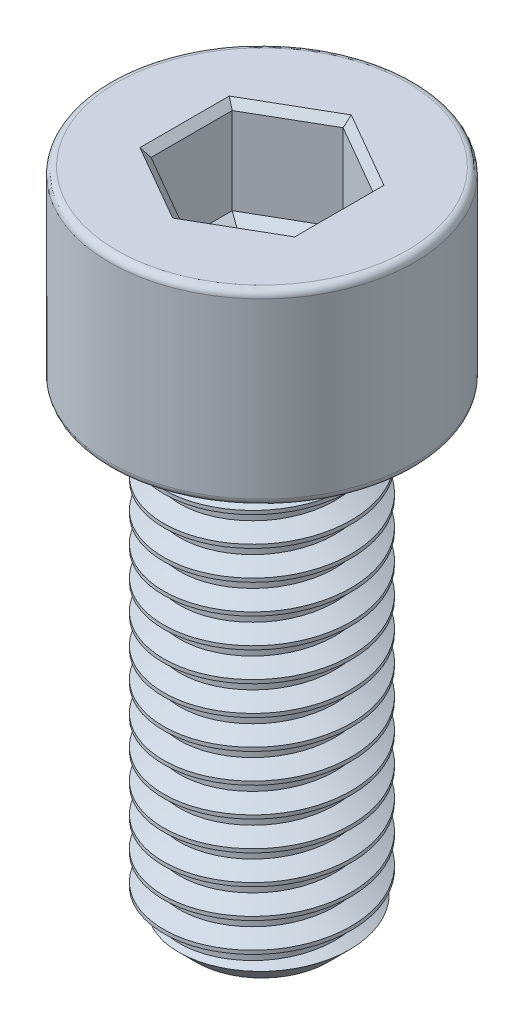
SolidWorks part; units mm, degrees
material "AISI Type A2 Tool Steel"
ref_plane "Front Plane" through (0, 0, 0) normal (0, 0, 1) x (1, 0, 0)
ref_plane "Top Plane" through (0, 0, 0) normal (0, 1, 0) x (1, 0, 0)
ref_plane "Right Plane" through (0, 0, 0) normal (1, 0, 0) x (0, 0, -1)
sketch "Sketch1" plane through (0, 0, 0) normal (0, 1, 0) x (1, 0, 0)
  circle A0 centre (0, 0) radius 4
  dimension "D1" = 8
extrude "Boss-Extrude1" add sketch "Sketch1" along normal blind 20
thread "Thread1" pitch 1.25 method cut profile "Thread Profile1" start angle 0, offset 1.25, length 0, pitch 1.25, diameter 8
ref_plane "Plane1" through (-4, 21.25, 0) normal (0, 0, 1) x (-1, 0, 0)
sketch "Thread Profile1" plane through (-4, 21.25, 0) normal (0, 0, 1) x (-1, 0, 0)
  line L0 (0, 0) -> (0, 1.25) construction
  line L11 (0, 0) -> (0, 1.0937)
  line L12 (0, 1.0937) -> (-0.6766, 0.7031)
  line L13 (-0.6766, 0.7031) -> (-0.6766, 0.3906)
  line L15 (-0.6766, 0.3906) -> (0, 0)
  line L17 (-0.6766, 0.5469) -> (0, 0.5469) construction
  point P2 (0, 0)
  dimension "Pitch" = 1.25
  dimension "Profile_Angle" = 60
  dimension "Profile_Land" = 0.3125
  dimension "Profile_Height" = 0.6766
sketch "Sketch2" plane through (0, 20, 0) normal (0, 1, 0) x (1, 0, 0)
  circle A0 centre (0, 0) radius 6.5
  dimension "D1" = 13
extrude "Boss-Extrude2" add sketch "Sketch2" along normal blind 8
sketch "Sketch5" plane through (0, 0, 0) normal (0, 0, 1) x (1, 0, 0)
  line L0 (0, 0) -> (0, 0.9986) construction
  line L1 (0, 0) -> (4.01, 0) construction
  line L2 (4.01, 0) -> (4.01, 1.2)
  line L3 (4.01, 1.2) -> (2.81, 0)
  line L4 (2.81, 0) -> (4.01, 0)
  dimension "D1" = 1.2
  dimension "D2" = 45
  dimension "D3" = 4.01
revolve "Cut-Revolve1" cut sketch "Sketch5" angle 360 about L0
fillet "Fillet1" radius 0.3 2 edges at (0, 28, 6.5) (0, 20, 6.5)
sketch "Sketch6" plane through (0, 28, 0) normal (0, 1, 0) x (1, 0, 0)
  line L1 (0, 3.4641) -> (-3, 1.7321)
  line L2 (-3, 1.7321) -> (-3, -1.7321)
  line L3 (-3, -1.7321) -> (0, -3.4641)
  line L4 (0, -3.4641) -> (3, -1.7321)
  line L5 (3, -1.7321) -> (3, 1.7321)
  line L6 (3, 1.7321) -> (0, 3.4641)
  circle A0 centre (0, 0) radius 3 construction
  dimension "D1" = 6
extrude "Cut-Extrude1" cut sketch "Sketch6" against normal blind 4
chamfer "Chamfer1" distance 0.3 angle 45 6 edges at (-3, 28, 0) (-1.5, 28, 2.5981) (1.5, 28, 2.5981) (3, 28, 0) (1.5, 28, -2.5981) (-1.5, 28, -2.5981)
sketch "Sketch7" plane through (0, 24, 0) normal (0, 1, 0) x (1, 0, 0)
  line L1 (0, 3.4641) -> (-3, 1.7321)
  line L2 (-3, 1.7321) -> (-3, -1.7321)
  line L3 (-3, -1.7321) -> (0, -3.4641)
  line L4 (0, -3.4641) -> (3, -1.7321)
  line L5 (3, -1.7321) -> (3, 1.7321)
  line L6 (3, 1.7321) -> (0, 3.4641)
  circle A0 centre (0, 0) radius 3 construction
extrude "Cut-Extrude2" cut sketch "Sketch7" against normal blind 0.4 draft 60
